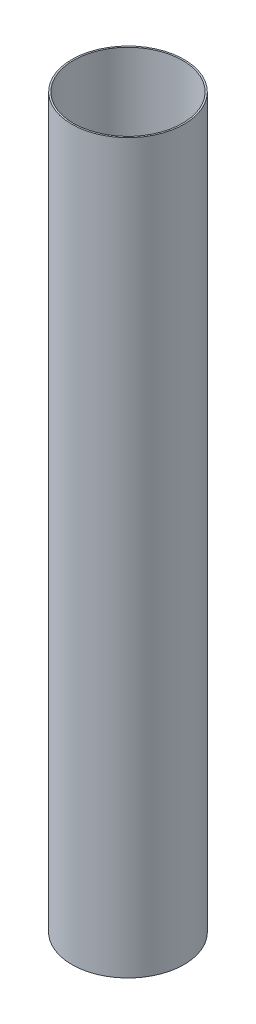
SolidWorks part; units mm, degrees
material "E-Glass Fiber"
ref_plane "Front Plane" through (0, 0, 0) normal (0, 0, 1) x (1, 0, 0)
ref_plane "Top Plane" through (0, 0, 0) normal (0, 1, 0) x (1, 0, 0)
ref_plane "Right Plane" through (0, 0, 0) normal (1, 0, 0) x (0, 0, -1)
sketch "Body Tube Profile" plane through (0, 0, 0) normal (0, 1, 0) x (1, 0, 0)
  circle A0 centre (0, 0) radius 76.2
  circle A1 centre (0, 0) radius 78.359
  dimension "D1" = 152.4
  dimension "D2" = 156.718
extrude "Body Tube Extrustion" add sketch "Body Tube Profile" along normal blind 1016
equation "\"Length\"=40"
equation "\"Outer Diameter\"= 6.17"
equation "\"Inner Diameter\"= 6"
equation "\"Wall Thickness\"= 0.085"
equation "\"D1@Body Tube Profile\" = \"Inner Diameter\""
equation "\"D2@Body Tube Profile\" = \"Outer Diameter\""
equation "\"D1@Body Tube Extrustion\" = \"Length\""
